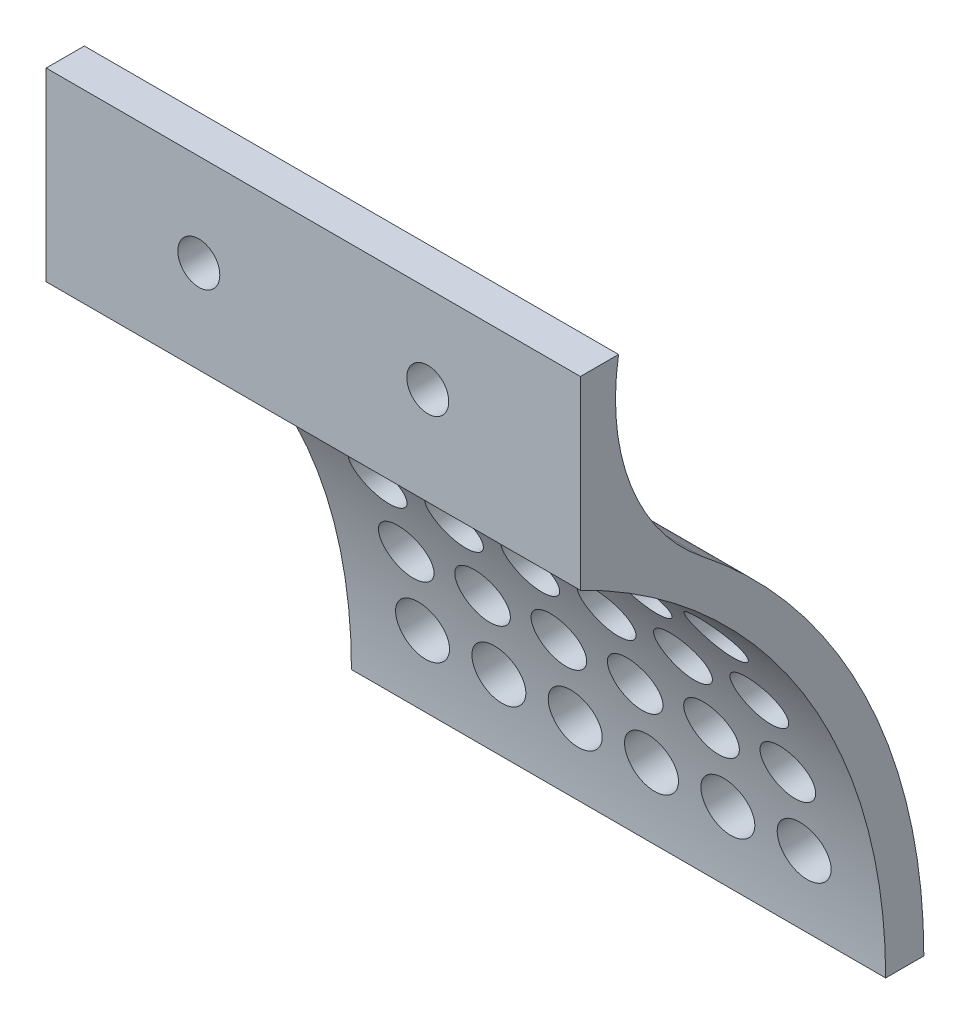
SolidWorks part; units mm, degrees
ref_plane "Alzado" through (0, 0, 0) normal (0, 0, 1) x (1, 0, 0)
ref_plane "Planta" through (0, 0, 0) normal (0, 1, 0) x (1, 0, 0)
ref_plane "Vista lateral" through (0, 0, 0) normal (1, 0, 0) x (0, 0, -1)
sketch "Croquis1" plane through (0, 0, 0) normal (1, 0, 0) x (0, 0, -1)
  line L0 (-25.1938, 53.195) -> (-20.1938, 53.195)
  line L2 (-25.1938, 53.195) -> (-25.1938, 28.9376)
  line L3 (14.8062, -35.0624) -> (19.8062, -35.0624)
  line L4 (-20.1938, 53.195) -> (-20.1938, 31.9898) construction
  arc A0 (-9.183, 24.7505) -> (19.8062, -35.0624) centre (-56.3938, -35.0624) cw
  arc A1 (-25.1938, 28.9376) -> (14.8062, -35.0624) centre (-56.3938, -35.0624) cw
  arc A2 (-20.1938, 31.9898) -> (19.8062, -35.0624) centre (-56.3938, -35.0624) cw construction
  arc A3 (-20.1938, 53.195) -> (-9.183, 24.7505) centre (9.4039, 48.2989) ccw
  dimension "D4" = 30
  dimension "D2" = 64
  dimension "D1" = 5
  dimension "D3" = 40
extrude "Saliente-Extruir1" add sketch "Croquis1" along normal blind 70
sketch "Croquis2" plane through (0, 0, 25.1938) normal (0, 0, 1) x (1, 0, 0)
  line L0 (0, 53.195) -> (0, 28.9376) construction
  line L1 (0, 53.195) -> (0, 28.9376)
  line L2 (70, 53.195) -> (70, 28.9376) construction
  circle A0 centre (20, 41.0663) radius 2.75
  circle A1 centre (50, 41.7171) radius 2.75
  point P8 (0, 41.0663)
  dimension "D1" = 5.5
  dimension "D2" = 20
  dimension "D3" = 20
ref_plane "Plano1" through (0, 0, -19.8062) normal (0, 0, 1) x (1, 0, 0)
sketch "Croquis3" plane through (0, 0, -19.8062) normal (0, 0, 1) x (1, 0, 0)
  line L0 (70, -35.0624) -> (70, 24.7505) construction
  line L1 (70, 24.7505) -> (0, 24.7505) construction
  circle A0 centre (60, 14.7505) radius 3.5
  circle A1 centre (50, 14.7505) radius 3.5
  circle A2 centre (40, 14.7505) radius 3.5
  circle A3 centre (30, 14.7505) radius 3.5
  circle A4 centre (20, 14.7505) radius 3.5
  circle A5 centre (10, 14.7505) radius 3.5
  circle A6 centre (50, 4.7505) radius 3.5
  circle A7 centre (40, 4.7505) radius 3.5
  circle A8 centre (30, 4.7505) radius 3.5
  circle A9 centre (20, 4.7505) radius 3.5
  circle A10 centre (10, 4.7505) radius 3.5
  circle A11 centre (50, -5.2495) radius 3.5
  circle A12 centre (40, -5.2495) radius 3.5
  circle A13 centre (30, -5.2495) radius 3.5
  circle A14 centre (20, -5.2495) radius 3.5
  circle A15 centre (10, -5.2495) radius 3.5
  circle A16 centre (60, 4.7505) radius 3.5
  circle A17 centre (60, -5.2495) radius 3.5
  circle A18 centre (20, -5.2495) radius 3.5
  circle A19 centre (30, -5.2495) radius 3.5
  circle A20 centre (40, -5.2495) radius 3.5
  circle A21 centre (50, -5.2495) radius 3.5
  circle A22 centre (60, -5.2495) radius 3.5
  circle A23 centre (20, -15.2495) radius 3.5
  circle A24 centre (30, -15.2495) radius 3.5
  circle A25 centre (40, -15.2495) radius 3.5
  circle A26 centre (50, -15.2495) radius 3.5
  circle A27 centre (60, -15.2495) radius 3.5
  circle A28 centre (20, -25.2495) radius 3.5
  circle A29 centre (30, -25.2495) radius 3.5
  circle A30 centre (40, -25.2495) radius 3.5
  circle A31 centre (50, -25.2495) radius 3.5
  circle A32 centre (60, -25.2495) radius 3.5
  circle A33 centre (10, -15.2495) radius 3.5
  circle A34 centre (10, -25.2495) radius 3.5
  circle A65 centre (10, 4.7505) radius 3.5
  circle A66 centre (10, -5.2495) radius 3.5
  circle A67 centre (10, -15.2495) radius 3.5
  circle A68 centre (10, -25.2495) radius 3.5
  circle A69 centre (0, 14.7505) radius 3.5 [skipped]
  circle A70 centre (-10, 14.7505) radius 3.5 [skipped]
  circle A71 centre (-20, 14.7505) radius 3.5 [skipped]
  circle A72 centre (-30, 14.7505) radius 3.5 [skipped]
  circle A73 centre (-40, 14.7505) radius 3.5 [skipped]
  circle A74 centre (-50, 14.7505) radius 3.5 [skipped]
  circle A75 centre (0, 4.7505) radius 3.5 [skipped]
  circle A76 centre (-10, 4.7505) radius 3.5 [skipped]
  circle A77 centre (-20, 4.7505) radius 3.5 [skipped]
  circle A78 centre (-30, 4.7505) radius 3.5 [skipped]
  circle A79 centre (-40, 4.7505) radius 3.5 [skipped]
  circle A80 centre (-50, 4.7505) radius 3.5 [skipped]
  circle A81 centre (0, -5.2495) radius 3.5 [skipped]
  circle A82 centre (-10, -5.2495) radius 3.5 [skipped]
  circle A83 centre (-20, -5.2495) radius 3.5 [skipped]
  circle A84 centre (-30, -5.2495) radius 3.5 [skipped]
  circle A85 centre (-40, -5.2495) radius 3.5 [skipped]
  circle A86 centre (-50, -5.2495) radius 3.5 [skipped]
  circle A87 centre (0, -15.2495) radius 3.5 [skipped]
  circle A88 centre (-10, -15.2495) radius 3.5 [skipped]
  circle A89 centre (-20, -15.2495) radius 3.5 [skipped]
  circle A90 centre (-30, -15.2495) radius 3.5 [skipped]
  circle A91 centre (-40, -15.2495) radius 3.5 [skipped]
  circle A92 centre (-50, -15.2495) radius 3.5 [skipped]
  circle A93 centre (0, -25.2495) radius 3.5 [skipped]
  circle A94 centre (-10, -25.2495) radius 3.5 [skipped]
  circle A95 centre (-20, -25.2495) radius 3.5 [skipped]
  circle A96 centre (-30, -25.2495) radius 3.5 [skipped]
  circle A97 centre (-40, -25.2495) radius 3.5 [skipped]
  circle A98 centre (-50, -25.2495) radius 3.5 [skipped]
  dimension "D1" = 7
  dimension "D2" = 10
  dimension "D3" = 10
  dimension "D4" = 6
  dimension "D5" = 3
  dimension "D6" = 6
  dimension "D7" = 3
  dimension "D8" = 7
  dimension "D9" = 5
extrude "Cortar-Extruir3" cut sketch "Croquis3" along normal blind 65 contours A0 | A1 | A2 | A3 | A4 | A5 | A16 | A6 | A17 | A11 | A12 | A7 | A8 | A9 | A13 | A14 | A15 | A10 | A23 | A33 | A34 | A28 | A24 | A25 | A30 | A29 | A26 | A31 | A27 | A32 region at (60, 14.7505, -19.8062) region at (50, 14.7505, -19.8062) region at (40, 14.7505, -19.8062) region at (30, 14.7505, -19.8062) region at (20, 14.7505, -19.8062) region at (10, 14.7505, -19.8062) region at (50, 4.7505, -19.8062) region at (40, 4.7505, -19.8062) region at (30, 4.7505, -19.8062) region at (20, 4.7505, -19.8062) region at (10, 4.7505, -19.8062) region at (50, -5.2495, -19.8062) region at (40, -5.2495, -19.8062) region at (30, -5.2495, -19.8062) region at (20, -5.2495, -19.8062) region at (10, -5.2495, -19.8062) region at (60, 4.7505, -19.8062) region at (60, -5.2495, -19.8062) region at (20, -15.2495, -19.8062) region at (30, -15.2495, -19.8062) region at (40, -15.2495, -19.8062) region at (50, -15.2495, -19.8062) region at (60, -15.2495, -19.8062) region at (20, -25.2495, -19.8062) region at (30, -25.2495, -19.8062) region at (40, -25.2495, -19.8062) region at (50, -25.2495, -19.8062) region at (60, -25.2495, -19.8062) region at (10, -15.2495, -19.8062) region at (10, -25.2495, -19.8062)
extrude "Cortar-Extruir4" cut sketch "Croquis2" against normal blind 65 contours A0 | A1 region at (20, 41.0663, 25.1938)
